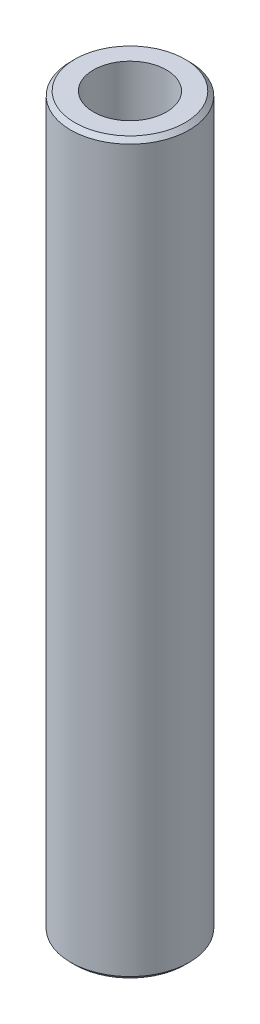
SolidWorks part; units mm, degrees
ref_plane "Front Plane" through (0, 0, 0) normal (0, 0, 1) x (1, 0, 0)
ref_plane "Top Plane" through (0, 0, 0) normal (0, 1, 0) x (1, 0, 0)
ref_plane "Right Plane" through (0, 0, 0) normal (1, 0, 0) x (0, 0, -1)
sketch "Sketch1" plane through (0, 0, 0) normal (0, 1, 0) x (1, 0, 0)
  circle A0 centre (0, 0) radius 35
  dimension "SHAFT_OD" = 70
extrude "Boss-Extrude1" add sketch "Sketch1" along normal blind 430.6092
sketch "Sketch2" plane through (0, 0, 0) normal (0, 1, 0) x (1, 0, 0)
  circle A0 centre (0, 0) radius 21.5471
  dimension "BORE_D" = 43.0943
extrude "Cut-Extrude1" cut sketch "Sketch2" along normal through all
chamfer "Chamfer1" distance 2.4897 angle 45 2 edges at (0, 430.6092, 35) (0, 0, 35)
